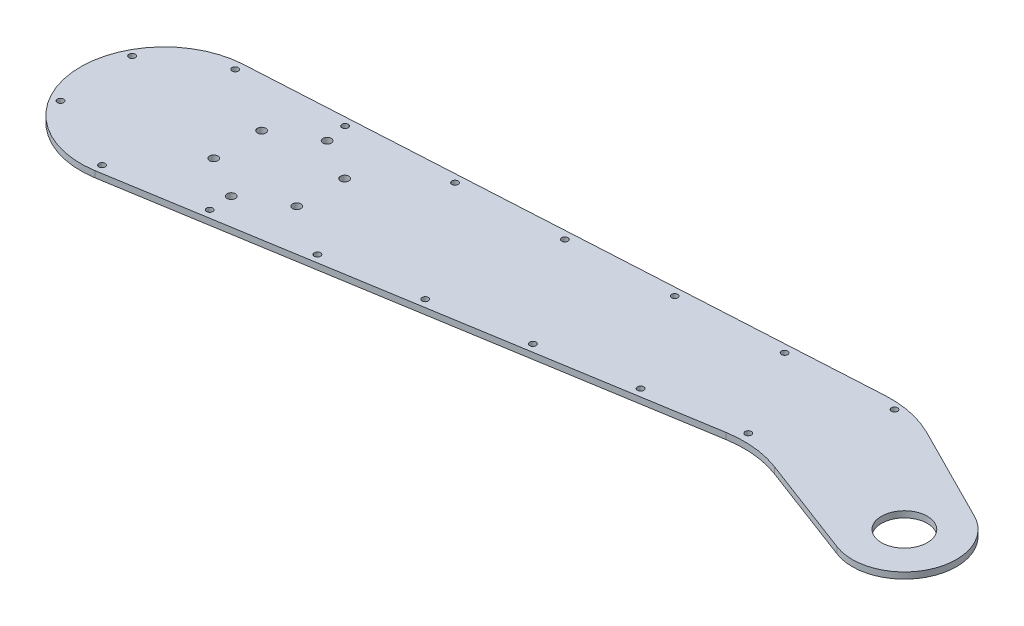
SolidWorks part; units mm, degrees
ref_plane "Front Plane" through (0, 0, 0) normal (0, 0, 1) x (1, 0, 0)
ref_plane "Top Plane" through (0, 0, 0) normal (0, 1, 0) x (1, 0, 0)
ref_plane "Right Plane" through (0, 0, 0) normal (1, 0, 0) x (0, 0, -1)
sketch "Sketch1" plane through (0, 0, 0) normal (0, 1, 0) x (1, 0, 0)
  line L0 (0, 0) -> (300, 0) construction
  line L1 (0, 0) -> (0, 37.5) construction
  line L2 (-2.1002, 37.4411) -> (6.0625, -37.0067) construction
  line L3 (311.2679, 22.3167) -> (291.1646, -23.3867) construction
  line L4 (300, 0) -> (300, 25) construction
  line L5 (-2.1002, 37.4411) -> (701.376, 76.9007)
  line L6 (701.376, 76.9007) -> (6.0625, -37.0067)
  line L7 (291.1646, -23.3867) -> (230.0775, -0.3082)
  line L8 (311.2679, 22.3167) -> (252.9755, 51.7489)
  line L9 (252.9755, 51.7489) -> (230.0775, -0.3082) construction
  line L10 (-2.1002, 37.4411) -> (-51.9511, 34.6449)
  line L11 (-43.21, -45.0786) -> (6.0625, -37.0067)
  line L12 (-49.7021, -5.4495) -> (0, 0) construction
  line L13 (0, 0) -> (701.376, 76.9007) construction
  circle A0 centre (0, 0) radius 37.5
  circle A1 centre (300, 0) radius 11
  circle A2 centre (300, 0) radius 25
  circle A3 centre (0, 0) radius 23 construction
  circle A4 centre (0, 23) radius 2
  circle A5 centre (19.9186, 11.5) radius 2
  circle A6 centre (19.9186, -11.5) radius 2
  circle A7 centre (0, -23) radius 2
  circle A8 centre (-19.9186, -11.5) radius 2
  circle A9 centre (-19.9186, 11.5) radius 2
  arc A10 (-51.9511, 34.6449) -> (-43.21, -45.0786) centre (-49.7021, -5.4495) ccw
  point P11 (325.211, 15.2767)
  point P31 (0, 0)
  dimension "D2" = 75
  dimension "D3" = 22
  dimension "D4" = 50
  dimension "D7" = 46
  dimension "D8" = 4
  dimension "D1" = 300
  dimension "D5" = 150
  dimension "D6" = 150
  dimension "D9" = 6
  dimension "D10" = 50
extrude "Boss-Extrude2" add sketch "Sketch1" along normal blind 3 contours A0 A3 | A2 L8 L5 A0 L6 | A2 L6 L7 | L6 A2 | L6 A2 A1 | L10 A10 L11 A0 region at (-54.9782, 0, 6.028) region at (145.5999, 0, -15.7285) region at (0, 0, 0) region at (297.2903, 0, -16.5403) region at (261.7379, 0, 4.4957) region at (323.2091, 0, -7.4087)
fillet "Fillet1" radius 50 2 edges at (230.0775, 1.5, 0.3082) (252.9755, 1.5, -51.7489)
sketch "Sketch3" plane through (0, 3, 0) normal (0, 1, 0) x (1, 0, 0)
  line L0 (-49.6973, -5.493) -> (0, 0)
  line L1 (0, 0) -> (496.9735, 54.9302)
  dimension "D1" = 500
sketch "Sketch2" plane through (0, 3, 0) normal (0, 1, 0) x (1, 0, 0)
  line L0 (-51.7271, 30.6512) -> (238.7529, 46.9449) construction
  line L1 (-43.8567, -41.1312) -> (227.7136, 3.3579) construction
  line L2 (216.8562, -2.4741) -> (-43.21, -45.0786) construction
  line L3 (-51.9511, 34.6449) -> (239.599, 50.9986) construction
  line L4 (264.0889, 41.6567) -> (301.3029, 22.8671) construction
  line L5 (311.2679, 22.3167) -> (264.935, 45.7105) construction
  line L6 (239.599, 50.9986) -> (-51.9511, 34.6449) construction
  line L7 (-43.21, -45.0786) -> (216.8562, -2.4741) construction
  line L8 (-51.7271, 30.6512) -> (-49.7021, -5.4495) construction
  circle A0 centre (-49.7021, -5.4495) radius 36.1574 construction
  arc A24 (-51.9511, 34.6449) -> (-43.21, -45.0786) centre (-49.7021, -5.4495) ccw construction
  arc A25 (238.7529, 46.9449) -> (264.0889, 41.6567) centre (241.5532, -2.9767) cw construction
  circle A26 centre (-51.7271, 30.6512) radius 1.5
  circle A27 centre (-43.8567, -41.1312) radius 1.5
  circle A31 centre (-80.543, -24.3567) radius 1.5
  circle A32 centre (-82.0145, 11.4657) radius 1.5
  circle A33 centre (-48.7842, -40.9936) radius 1.5 [skipped]
  circle A34 centre (-18.4969, -21.8081) radius 1.5 [skipped]
  circle A35 centre (-19.9683, 14.0143) radius 1.5 [skipped]
  circle A36 centre (-1.8056, 33.4514) radius 1.5
  circle A37 centre (48.1159, 36.2516) radius 1.5
  circle A38 centre (98.0375, 39.0518) radius 1.5
  circle A39 centre (147.959, 41.852) radius 1.5
  circle A40 centre (197.8805, 44.6522) radius 1.5
  circle A41 centre (247.802, 47.4524) radius 1.5
  circle A48 centre (0.5513, -33.8562) radius 1.5
  circle A49 centre (44.9594, -26.5812) radius 1.5
  circle A50 centre (89.3674, -19.3062) radius 1.5
  circle A51 centre (133.7755, -12.0312) radius 1.5
  circle A52 centre (178.1835, -4.7562) radius 1.5
  circle A53 centre (222.5916, 2.5188) radius 1.5
  point P29 (0, 0)
  point P32 (-50.2557, -5.1712)
  dimension "D1" = 4
  dimension "D2" = 4
  dimension "D3" = 4
  dimension "D4" = 50
  dimension "D6" = 3
  dimension "D5" = 4
  dimension "D7" = 6
  dimension "D8" = 7
  dimension "D9" = 7
extrude "Cut-Extrude1" cut sketch "Sketch2" against normal blind 10
